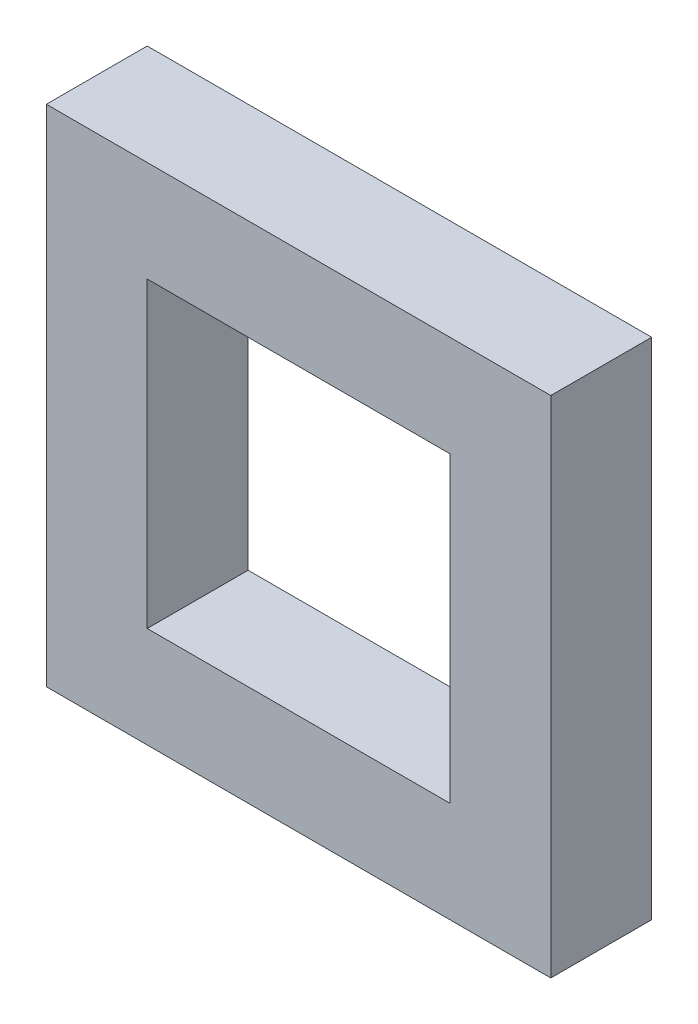
SolidWorks part; units mm, degrees
material "Balsa"
ref_plane "Front Plane" through (0, 0, 0) normal (0, 0, 1) x (1, 0, 0)
ref_plane "Top Plane" through (0, 0, 0) normal (0, 1, 0) x (1, 0, 0)
ref_plane "Right Plane" through (0, 0, 0) normal (1, 0, 0) x (0, 0, -1)
sketch "Sketch1" plane through (0, 0, 0) normal (0, 0, 1) x (1, 0, 0)
  line L0 (0, 0) -> (0, 31.75)
  line L6 (31.75, 31.75) -> (31.75, 0)
  line L7 (31.75, 0) -> (0, 0)
  line L8 (6.35, 6.35) -> (25.4, 6.35)
  line L9 (6.35, 6.35) -> (6.35, 25.4)
  line L10 (6.35, 25.4) -> (25.4, 25.4)
  line L11 (25.4, 6.35) -> (25.4, 25.4)
  line L12 (31.75, 31.75) -> (0, 31.75)
  point P13 (15.875, 0)
  dimension "D2" = 19.05
  dimension "D3" = 19.05
  dimension "D4" = 6.35
  dimension "D5" = 6.35
  dimension "D6" = 6.35
  dimension "D1" = 6.35
extrude "Boss-Extrude1" add sketch "Sketch1" along normal blind 6.35
equation "\"D1@Sketch1\"=\"D5@Sketch1\""
equation "\"D6@Sketch1\"=\"D5@Sketch1\""
equation "\"D4@Sketch1\"=\"D5@Sketch1\""
equation "\"D2@Sketch1\"=\"D3@Sketch1\""
